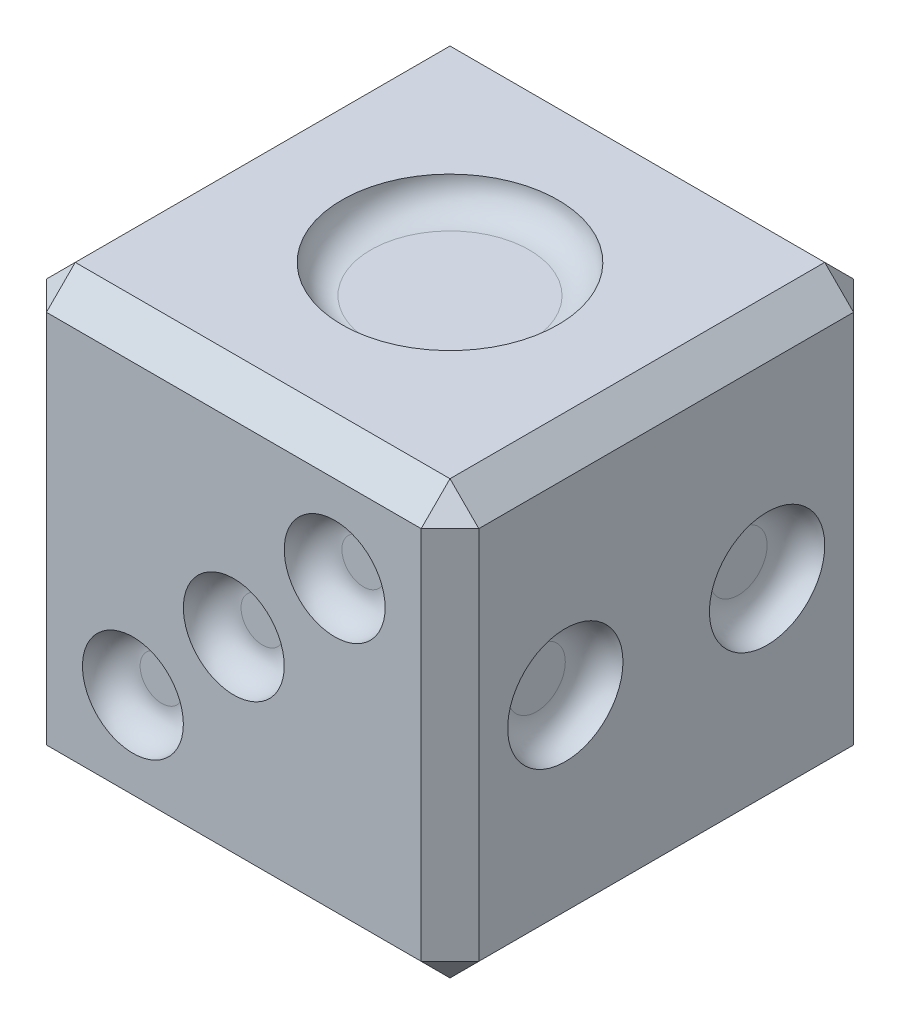
SolidWorks part; units mm, degrees
ref_plane "正面" through (0, 0, 0) normal (0, 0, 1) x (1, 0, 0)
ref_plane "平面" through (0, 0, 0) normal (0, 1, 0) x (1, 0, 0)
ref_plane "右側面" through (0, 0, 0) normal (1, 0, 0) x (0, 0, -1)
sketch "ｽｹｯﾁ2" plane through (0, 0, 0) normal (0, 1, 0) x (1, 0, 0)
  line L1 (0, 0) -> (30, 0)
  line L2 (0, 0) -> (0, 30)
  line L3 (0, 30) -> (30, 30)
  line L4 (30, 0) -> (30, 30)
  dimension "D1" = 30
  dimension "D2" = 30
extrude "ﾎﾞｽ - 押し出し1" add sketch "ｽｹｯﾁ2" along normal blind 30
chamfer "面取り1" distance 2 angle 45 12 edges at (0, 15, 0) (30, 15, 0) (30, 15, -30) (15, 30, -30) (30, 30, -15) (15, 30, 0) (0, 30, -15) (0, 15, -30) (15, 0, -30) (30, 0, -15) (15, 0, 0) (0, 0, -15)
sketch "ｽｹｯﾁ3" plane through (0, 30, 0) normal (0, 1, 0) x (1, 0, 0)
  line L0 (2, 28) -> (2, 2) construction
  line L1 (2, 2) -> (28, 2) construction
  circle A0 centre (15, 15) radius 7.5
  dimension "D1" = 15
  dimension "D2" = 13
  dimension "D3" = 13
extrude "ｶｯﾄ - 押し出し1" cut sketch "ｽｹｯﾁ3" against normal blind 2
fillet "ﾌｨﾚｯﾄ1" radius 2 1 edges at (15, 28, -7.5)
sketch "ｽｹｯﾁ4" plane through (0, 0, 0) normal (0, 0, 1) x (1, 0, 0)
  line L0 (0, 2) -> (0, 28) construction
  line L1 (28, 0) -> (2, 0) construction
  line L2 (2, 30) -> (28, 30) construction
  line L3 (30, 28) -> (30, 2) construction
  circle A0 centre (8, 8) radius 3.5
  circle A1 centre (15, 15) radius 3.5
  circle A2 centre (22, 22) radius 3.5
  dimension "D3" = 7
  dimension "D6" = 7
  dimension "D9" = 7
  dimension "D1" = 8
  dimension "D2" = 8
  dimension "D4" = 8
  dimension "D5" = 8
  dimension "D7" = 15
  dimension "D8" = 15
extrude "ｶｯﾄ - 押し出し2" cut sketch "ｽｹｯﾁ4" against normal blind 2
fillet "ﾌｨﾚｯﾄ2" radius 2 3 edges at (11.5, 8, -2) (18.5, 15, -2) (25.5, 22, -2)
sketch "ｽｹｯﾁ6" plane through (0, 0, -30) normal (0, 0, -1) x (-1, 0, 0)
  line L0 (-2, 0) -> (-28, 0) construction
  line L1 (-30, 2) -> (-30, 28) construction
  line L2 (0, 28) -> (0, 2) construction
  line L3 (-28, 30) -> (-2, 30) construction
  circle A0 centre (-22, 8) radius 3.5
  circle A2 centre (-8, 22) radius 3.5
  dimension "D1" = 7
  dimension "D7" = 7
  dimension "D2" = 8
  dimension "D3" = 8
  dimension "D8" = 8
  dimension "D9" = 8
extrude "ｶｯﾄ - 押し出し3" cut sketch "ｽｹｯﾁ6" against normal blind 2
sketch "ｽｹｯﾁ7" plane through (30, 0, 0) normal (1, 0, 0) x (0, 0, -1)
  line L0 (2, 30) -> (28, 30) construction
  line L1 (30, 28) -> (30, 2) construction
  line L2 (0, 2) -> (0, 28) construction
  circle A0 centre (8, 15) radius 4
  circle A1 centre (22, 15) radius 4
  dimension "D3" = 8
  dimension "D4" = 8
  dimension "D1" = 15
  dimension "D2" = 15
  dimension "D5" = 8
  dimension "D6" = 8
extrude "ｶｯﾄ - 押し出し4" cut sketch "ｽｹｯﾁ7" against normal blind 2
fillet "ﾌｨﾚｯﾄ4" radius 2 2 edges at (28, 15, -26) (28, 15, -12)
sketch "ｽｹｯﾁ8" plane through (0, 0, 0) normal (-1, 0, 0) x (0, 0, 1)
  line L0 (-30, 2) -> (-30, 28) construction
  line L1 (0, 28) -> (0, 2) construction
  line L2 (-28, 30) -> (-2, 30) construction
  line L3 (-2, 0) -> (-28, 0) construction
  circle A0 centre (-22, 22) radius 3.5
  circle A1 centre (-8, 22) radius 3.5
  circle A2 centre (-22, 8) radius 3.5
  circle A3 centre (-8, 8) radius 3.5
  dimension "D1" = 7
  dimension "D2" = 7
  dimension "D3" = 7
  dimension "D4" = 7
  dimension "D5" = 8
  dimension "D6" = 8
  dimension "D7" = 8
  dimension "D8" = 8
  dimension "D9" = 8
  dimension "D10" = 8
  dimension "D11" = 8
  dimension "D12" = 8
extrude "ｶｯﾄ - 押し出し5" cut sketch "ｽｹｯﾁ8" against normal blind 2
fillet "ﾌｨﾚｯﾄ5" radius 2 4 edges at (2, 8, -18.5) (2, 8, -4.5) (2, 22, -4.5) (2, 22, -18.5)
sketch "ｽｹｯﾁ9" plane through (0, 0, 0) normal (0, -1, 0) x (1, 0, 0)
  line L0 (2, 0) -> (28, 0) construction
  line L1 (0, -28) -> (0, -2) construction
  line L2 (28, -30) -> (2, -30) construction
  line L3 (30, -2) -> (30, -28) construction
  circle A1 centre (8, -7) radius 3.5
  circle A2 centre (22, -7) radius 3.5
  circle A3 centre (22, -23) radius 3.5
  circle A4 centre (8, -23) radius 3.5
  circle A5 centre (8, -15) radius 3.5
  circle A6 centre (22, -15) radius 3.5
  dimension "D3" = 7
  dimension "D4" = 7
  dimension "D5" = 7
  dimension "D6" = 7
  dimension "D7" = 7
  dimension "D2" = 7
  dimension "D8" = 8
  dimension "D9" = 7
  dimension "D10" = 7
  dimension "D11" = 8
  dimension "D12" = 7
  dimension "D13" = 8
  dimension "D14" = 8
  dimension "D15" = 7
  dimension "D16" = 15
  dimension "D17" = 15
extrude "ｶｯﾄ - 押し出し6" cut sketch "ｽｹｯﾁ9" against normal blind 2
sketch "ｽｹｯﾁ12" plane through (0, 0, 0) normal (-1, 0, 0) x (0, 0, 1)
  line L0 (0, 28) -> (0, 2) construction
  line L1 (-28, 30) -> (-2, 30) construction
  circle A0 centre (-15, 15) radius 3.5
  dimension "D1" = 7
  dimension "D2" = 15
  dimension "D3" = 15
extrude "ｶｯﾄ - 押し出し7" cut sketch "ｽｹｯﾁ12" against normal blind 2
fillet "ﾌｨﾚｯﾄ7" radius 2 1 edges at (2, 15, -11.5)
sketch "ｽｹｯﾁ13" plane through (0, 0, -30) normal (0, 0, -1) x (-1, 0, 0)
  line L0 (0, 28) -> (0, 2) construction
  line L1 (-2, 0) -> (-28, 0) construction
  line L2 (-30, 2) -> (-30, 28) construction
  circle A0 centre (-22, 22) radius 3.5
  circle A1 centre (-8, 8) radius 3.5
  circle A2 centre (-8, 22) radius 3.5 construction
  dimension "D1" = 7
  dimension "D2" = 7
  dimension "D3" = 8
  dimension "D4" = 8
  dimension "D5" = 8
  dimension "D6" = 8
  dimension "D7" = 8
extrude "ｶｯﾄ - 押し出し9" cut sketch "ｽｹｯﾁ13" against normal blind 2 contours A0 | A1
fillet "ﾌｨﾚｯﾄ8" radius 2 4 edges at (4.5, 8, -28) (18.5, 8, -28) (4.5, 22, -28) (18.5, 22, -28)
fillet "ﾌｨﾚｯﾄ9" radius 2 6 edges at (8, 2, -26.5) (22, 2, -26.5) (8, 2, -18.5) (22, 2, -18.5) (22, 2, -10.5) (8, 2, -10.5)
